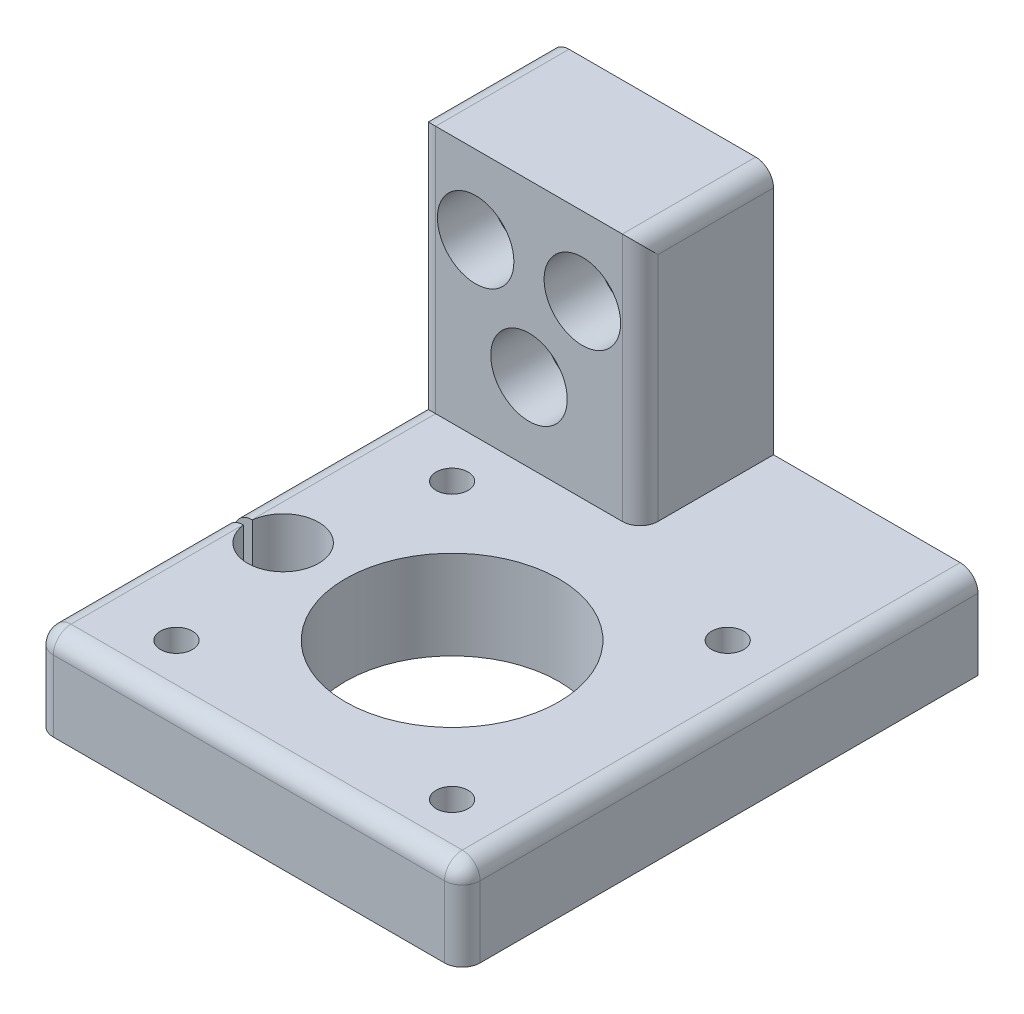
SolidWorks part; units mm, degrees
ref_plane "Front Plane" through (0, 0, 0) normal (0, 0, 1) x (1, 0, 0)
ref_plane "Top Plane" through (0, 0, 0) normal (0, 1, 0) x (1, 0, 0)
ref_plane "Right Plane" through (0, 0, 0) normal (1, 0, 0) x (0, 0, -1)
sketch "Sketch1" plane through (0, 0, 0) normal (0, 1, 0) x (1, 0, 0)
  line L0 (9.5, -20.65) -> (40.5, -20.65) construction
  line L1 (0, 0) -> (48, 0)
  line L2 (0, 0) -> (0, -58)
  line L3 (0, -58) -> (48, -58)
  line L4 (48, 0) -> (48, -58)
  line L5 (40.5, -20.65) -> (40.5, -51.65) construction
  line L6 (40.5, -51.65) -> (9.5, -51.65) construction
  line L7 (9.5, -51.65) -> (9.5, -20.65) construction
  line L8 (25, -36.15) -> (6, -36.15) construction
  line L9 (6, -36.15) -> (0, -36.15) construction
  line L11 (0, -35.65) -> (2.0314, -35.65)
  line L12 (0, -35.65) -> (0, -36.65)
  line L13 (0, -36.65) -> (2.0314, -36.65)
  line L14 (2.0314, -35.65) -> (2.0314, -36.65)
  circle A0 centre (9.5, -20.65) radius 1.8
  circle A1 centre (40.5, -20.65) radius 1.8
  circle A2 centre (40.5, -51.65) radius 1.8
  circle A3 centre (9.5, -51.65) radius 1.8
  circle A4 centre (25, -36.15) radius 12
  circle A5 centre (6, -36.15) radius 4
  dimension "D3" = 31
  dimension "D4" = 3.6
  dimension "D7" = 8
  dimension "D8" = 24
  dimension "D1" = 58
  dimension "D2" = 48
  dimension "D5" = 6.35
  dimension "D6" = 7.5
  dimension "D9" = 23
  dimension "D10" = 21.85
  dimension "D11" = 19
  dimension "D12" = 1
extrude "Boss-Extrude1" add sketch "Sketch1" along normal blind 10 contours A5 L11 L4 L1 L2 L3 L13 A4 A3 A2 A1 A0 region at (24, 0, 0.7529)
sketch "Sketch2" plane through (0, 0, 0) normal (1, 0, 0) x (0, 0, -1)
  line L1 (0, 10) -> (-15, 10)
  line L2 (0, 10) -> (0, 38)
  line L3 (0, 38) -> (-15, 38)
  line L4 (-15, 10) -> (-15, 38)
  dimension "D1" = 28
  dimension "D2" = 15
extrude "Boss-Extrude2" add sketch "Sketch2" along normal blind 25
sketch "Sketch3" plane through (0, 0, 15) normal (0, 0, 1) x (1, 0, 0)
  line L0 (6.5, 29.1962) -> (18.5, 29.1962) construction
  line L1 (18.5, 29.1962) -> (12.5, 18.8038) construction
  line L2 (12.5, 18.8038) -> (6.5, 29.1962) construction
  line L3 (12.5, 18.8038) -> (12.5, 10) construction
  line L4 (25, 10) -> (0, 10) construction
  line L5 (12.5, 29.1962) -> (12.5, 38) construction
  line L6 (25, 38) -> (0, 38) construction
  circle A0 centre (6.5, 29.1962) radius 2.8
  circle A1 centre (18.5, 29.1962) radius 2.8
  circle A2 centre (12.5, 18.8038) radius 2.8
  dimension "D1" = 12
  dimension "D2" = 5.6
extrude "Cut-Extrude1" cut sketch "Sketch3" against normal through all
sketch "Sketch4" plane through (0, 0, 15) normal (0, 0, 1) x (1, 0, 0)
  circle A0 centre (6.5, 29.1962) radius 4.3
  circle A1 centre (18.5, 29.1962) radius 4.3
  circle A2 centre (12.5, 18.8038) radius 4.3
  dimension "D1" = 8.6
extrude "Cut-Extrude2" cut sketch "Sketch4" against normal blind 6
fillet "Fillet1" radius 2 10 edges at (48, 5, 58) (0, 5, 58) (0, 10, 47.325) (24, 10, 58) (48, 10, 29) (0, 24, 15) (0, 38, 7.5) (25, 24, 15) (25, 38, 7.5) (0, 10, 25.325)
